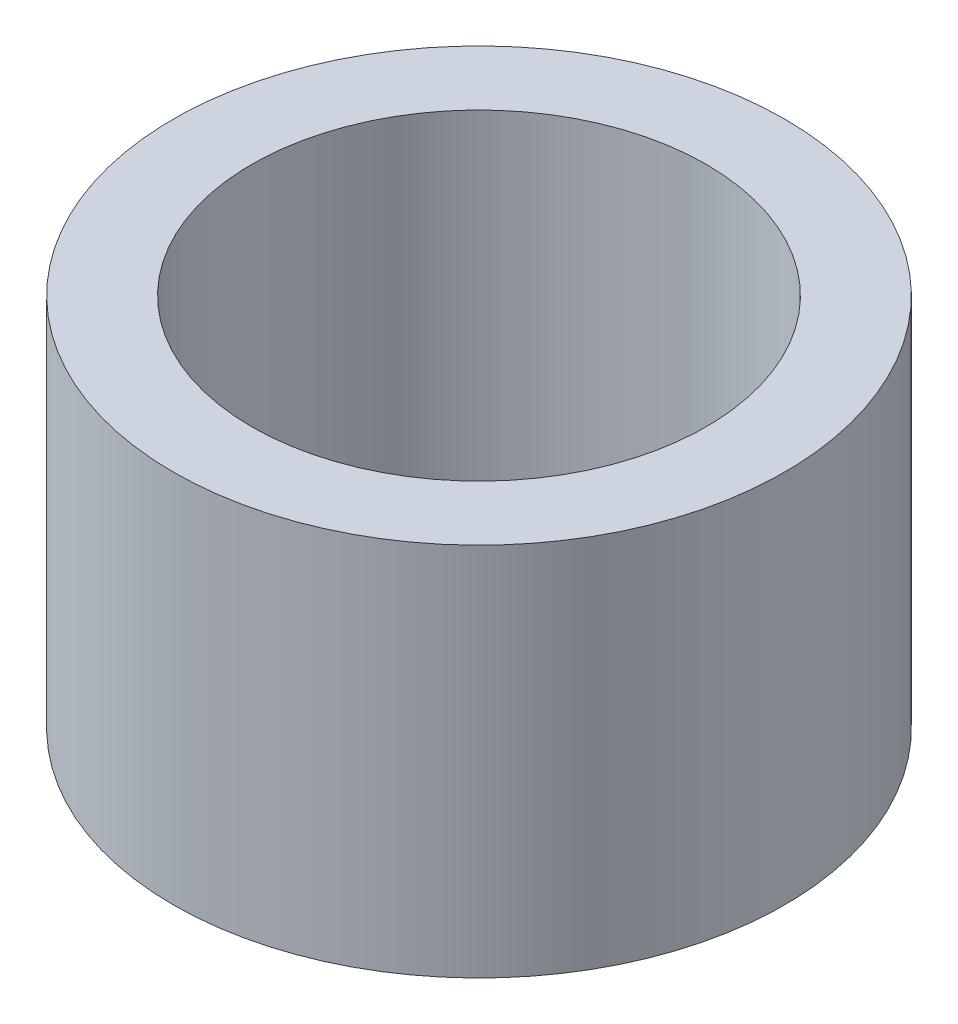
SolidWorks part; units mm, degrees
ref_plane "Front Plane" through (0, 0, 0) normal (0, 0, 1) x (1, 0, 0)
ref_plane "Top Plane" through (0, 0, 0) normal (0, 1, 0) x (1, 0, 0)
ref_plane "Right Plane" through (0, 0, 0) normal (1, 0, 0) x (0, 0, -1)
sketch "Sketch1" plane through (0, 0, 0) normal (0, 1, 0) x (1, 0, 0)
  circle A0 centre (0, 0) radius 25
  dimension "SLEEVE_OD" = 50
extrude "Boss-Extrude1" add sketch "Sketch1" along normal blind 30.6544
sketch "Sketch2" plane through (0, 0, 0) normal (0, 1, 0) x (1, 0, 0)
  circle A0 centre (0, 0) radius 18.5871
  dimension "BORE_D" = 37.1742
extrude "Cut-Extrude1" cut sketch "Sketch2" along normal through all
chamfer "Chamfer1" distance 3.2671 angle 45.103 rebuild error yes
